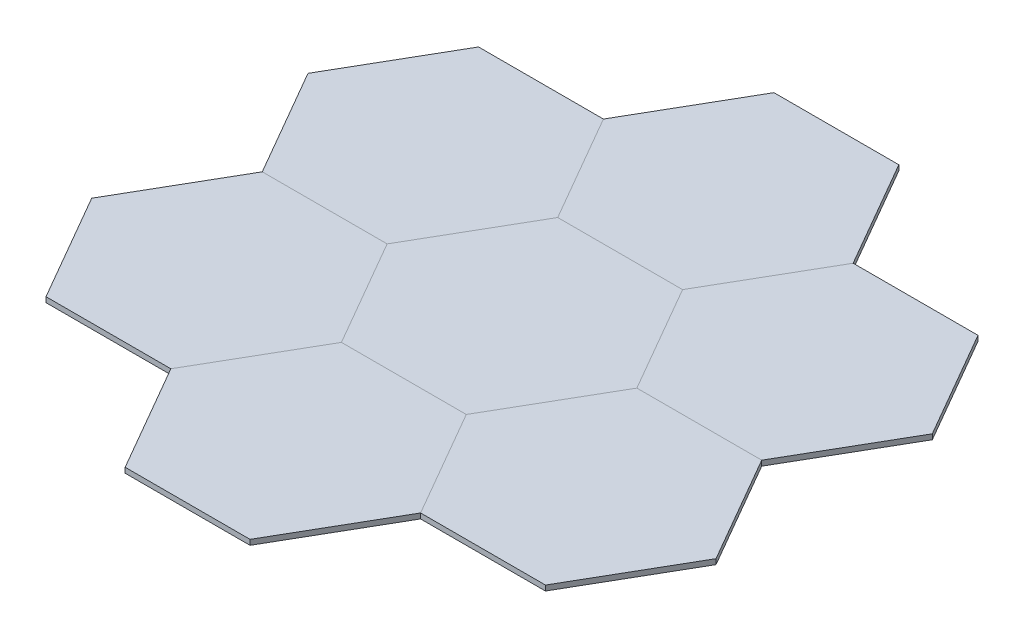
SolidWorks part; units mm, degrees
material "Cedar"
ref_plane "Front Plane" through (0, 0, 0) normal (0, 0, 1) x (1, 0, 0)
ref_plane "Top Plane" through (0, 0, 0) normal (0, 1, 0) x (1, 0, 0)
ref_plane "Right Plane" through (0, 0, 0) normal (1, 0, 0) x (0, 0, -1)
sketch "Sketch1" plane through (0, 0, 0) normal (0, 1, 0) x (1, 0, 0)
  line L0 (0, 0) -> (76.2, 0) construction
  line L1 (76.2, 0) -> (38.1, 65.9911)
  line L2 (38.1, 65.9911) -> (-38.1, 65.9911)
  line L3 (-38.1, 65.9911) -> (-76.2, 0)
  line L4 (-76.2, 0) -> (-38.1, -65.9911)
  line L5 (-38.1, -65.9911) -> (38.1, -65.9911)
  line L6 (38.1, -65.9911) -> (76.2, 0)
  circle A0 centre (0, 0) radius 65.9911 construction
  dimension "D1" = 76.2
extrude "Boss-Extrude1" add sketch "Sketch1" along normal blind 3.175
mirror "Mirror1" about plane through (38.1, 3.175, 65.9911) normal (-0.866, 0, -0.5) of bodies 101
ref_axis "Axis1" through (0, 0, 0) along (0, 1, 0)
pattern_circular "CirPattern1" count 6 over 360 about axis through (0, 0, 0) along (0, 1, 0) of bodies 102
